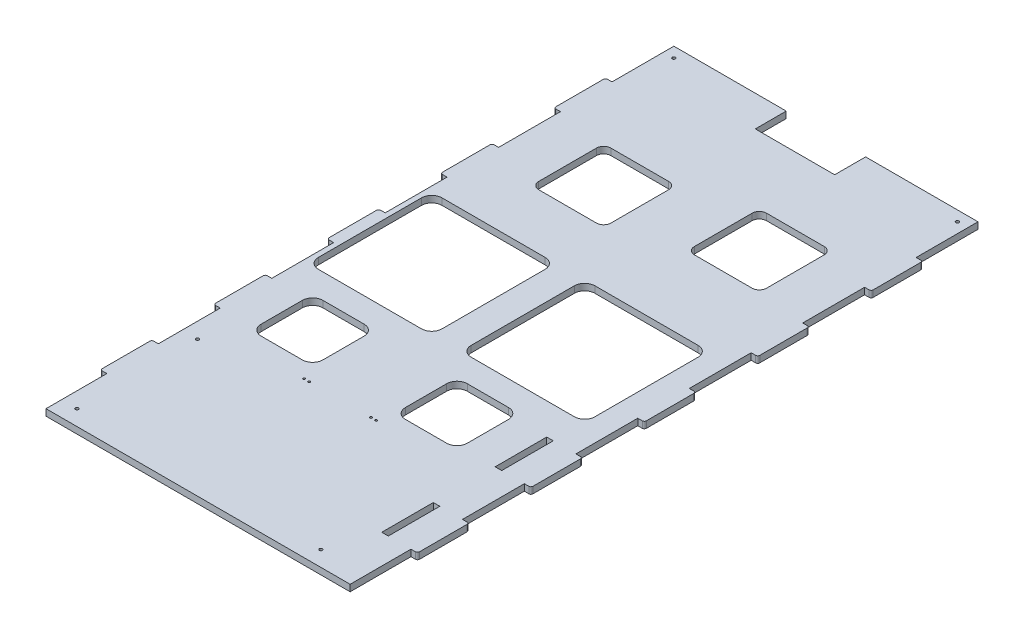
SolidWorks part; units mm, degrees
material "Beech"
ref_plane "Front Plane" through (0, 0, 0) normal (0, 0, 1) x (1, 0, 0)
ref_plane "Top Plane" through (0, 0, 0) normal (0, 1, 0) x (1, 0, 0)
ref_plane "Right Plane" through (0, 0, 0) normal (1, 0, 0) x (0, 0, -1)
sketch "Sketch1" plane through (0, 0, 0) normal (0, 1, 0) x (1, 0, 0)
  line L1 (0, 0) -> (295, 0)
  line L2 (0, 0) -> (0, 59)
  line L3 (0, 609) -> (295, 609)
  line L4 (295, 0) -> (295, 59)
  line L5 (0, 59) -> (-6.35, 59)
  line L7 (0, 109) -> (-6.35, 109)
  line L8 (-6.35, 59) -> (-6.35, 109)
  line L9 (0, 169) -> (-6.35, 169)
  line L10 (-6.35, 169) -> (-6.35, 219)
  line L11 (0, 219) -> (-6.35, 219)
  line L13 (0, 279) -> (-6.35, 279)
  line L14 (-6.35, 279) -> (-6.35, 329)
  line L15 (0, 329) -> (-6.35, 329)
  line L17 (0, 389) -> (-6.35, 389)
  line L18 (-6.35, 389) -> (-6.35, 439)
  line L19 (0, 439) -> (-6.35, 439)
  line L21 (0, 499) -> (-6.35, 499)
  line L22 (-6.35, 499) -> (-6.35, 549)
  line L23 (0, 549) -> (-6.35, 549)
  line L25 (295, 59) -> (301.35, 59)
  line L27 (295, 109) -> (301.35, 109)
  line L28 (301.35, 59) -> (301.35, 109)
  line L29 (295, 169) -> (301.35, 169)
  line L30 (301.35, 169) -> (301.35, 219)
  line L31 (295, 219) -> (301.35, 219)
  line L33 (295, 279) -> (301.35, 279)
  line L34 (301.35, 279) -> (301.35, 329)
  line L35 (295, 329) -> (301.35, 329)
  line L37 (295, 389) -> (301.35, 389)
  line L38 (301.35, 389) -> (301.35, 439)
  line L39 (295, 439) -> (301.35, 439)
  line L41 (295, 499) -> (301.35, 499)
  line L42 (301.35, 499) -> (301.35, 549)
  line L43 (295, 549) -> (301.35, 549)
  line L44 (0, 549) -> (0, 609)
  line L46 (0, 329) -> (0, 389)
  line L49 (0, 219) -> (0, 279)
  line L50 (0, 109) -> (0, 169)
  line L51 (295, 109) -> (295, 169)
  line L52 (295, 219) -> (295, 279)
  line L53 (295, 329) -> (295, 389)
  line L54 (295, 439) -> (295, 499)
  line L55 (295, 549) -> (295, 609)
  line L56 (0, 439) -> (0, 499)
  dimension "D1" = 609
  dimension "D2" = 295
  dimension "D3" = 6.35
  dimension "D4" = 50
  dimension "D5" = 59
  dimension "D7" = 60
  dimension "D8" = 50
  dimension "D9" = 6.35
  dimension "D11" = 59
  dimension "D12" = 60
  dimension "D6" = 5
  dimension "D10" = 5
extrude "Boss-Extrude1" add sketch "Sketch1" along normal blind 6.35
fillet "Fillet1" radius 2 20 edges at (301.35, 3.175, -549) (301.35, 3.175, -499) (301.35, 3.175, -439) (301.35, 3.175, -389) (301.35, 3.175, -329) (301.35, 3.175, -279) (301.35, 3.175, -219) (301.35, 3.175, -169) (301.35, 3.175, -109) (301.35, 3.175, -59) (-6.35, 3.175, -59) (-6.35, 3.175, -109) (-6.35, 3.175, -169) (-6.35, 3.175, -219) (-6.35, 3.175, -279) (-6.35, 3.175, -329) (-6.35, 3.175, -389) (-6.35, 3.175, -439) (-6.35, 3.175, -499) (-6.35, 3.175, -549)
sketch "Sketch2" plane through (0, 6.35, 0) normal (0, 1, 0) x (1, 0, 0)
  line L0 (266.65, 0) -> (266.65, 100) construction
  line L1 (0, 0) -> (295, 0) construction
  line L2 (0, 609) -> (0, 0) construction
  line L3 (295, 609) -> (295, 0) construction
  line L4 (0, 150) -> (266.65, 100) construction
  line L5 (266.65, 169) -> (266.65, 219)
  line L6 (266.65, 59) -> (273, 59)
  line L7 (266.65, 59) -> (266.65, 109)
  line L8 (266.65, 109) -> (273, 109)
  line L9 (273, 59) -> (273, 109)
  line L10 (266.65, 169) -> (273, 169)
  line L11 (273, 169) -> (273, 219)
  line L12 (266.65, 219) -> (273, 219)
  line L13 (0, 84.2124) -> (266.65, 84) construction
  line L14 (55.0424, 492.8768) -> (111.0424, 492.8768)
  line L15 (48.0424, 485.8768) -> (48.0424, 429.8768)
  line L16 (55.0424, 422.8768) -> (111.0424, 422.8768)
  line L17 (118.0424, 485.8768) -> (118.0424, 429.8768)
  line L18 (185.2335, 513.6581) -> (241.2335, 513.6581)
  line L19 (178.2335, 506.6581) -> (178.2335, 450.6581)
  line L20 (185.2335, 443.6581) -> (241.2335, 443.6581)
  line L21 (248.2335, 506.6581) -> (248.2335, 450.6581)
  line L22 (43.325, 225.298) -> (83.325, 225.298)
  line L23 (33.325, 215.298) -> (33.325, 175.298)
  line L24 (43.325, 165.298) -> (83.325, 165.298)
  line L25 (93.325, 215.298) -> (93.325, 175.298)
  line L26 (33.325, 225.298) -> (93.325, 165.298) construction
  line L27 (33.325, 165.298) -> (93.325, 225.298) construction
  line L32 (133.325, 0) -> (133.325, 609) construction
  line L33 (295, 609) -> (0, 609) construction
  line L34 (5, 369.1536) -> (125, 369.1536)
  line L35 (5, 369.1536) -> (5, 249.1536)
  line L36 (5, 249.1536) -> (125, 249.1536)
  line L37 (125, 369.1536) -> (125, 249.1536)
  line L38 (153, 369.4528) -> (273, 369.4528)
  line L39 (153, 369.4528) -> (153, 249.4528)
  line L40 (153, 249.4528) -> (273, 249.4528)
  line L41 (273, 369.4528) -> (273, 249.4528)
  line L42 (233.325, 165.298) -> (173.325, 225.298) construction
  line L43 (233.325, 225.298) -> (173.325, 165.298) construction
  line L44 (173.325, 215.298) -> (173.325, 175.298)
  line L45 (223.325, 165.298) -> (183.325, 165.298)
  line L46 (233.325, 215.298) -> (233.325, 175.298)
  line L47 (223.325, 225.298) -> (183.325, 225.298)
  line L48 (100, 150.298) -> (105, 150.298) construction
  line L49 (105, 150.298) -> (165, 150.298) construction
  line L50 (165, 150.298) -> (170, 150.298) construction
  line L51 (147.5, 609) -> (147.5, 0) construction
  line L52 (109, 609) -> (186, 609)
  line L53 (109, 609) -> (109, 579)
  line L54 (109, 579) -> (186, 579)
  line L55 (186, 609) -> (186, 579)
  line L56 (147.5, 609) -> (147.5, 579) construction
  arc A0 (48.0424, 429.8768) -> (55.0424, 422.8768) centre (55.0424, 429.8768) ccw
  arc A1 (111.0424, 422.8768) -> (118.0424, 429.8768) centre (111.0424, 429.8768) ccw
  arc A2 (111.0424, 492.8768) -> (118.0424, 485.8768) centre (111.0424, 485.8768) cw
  arc A3 (55.0424, 492.8768) -> (48.0424, 485.8768) centre (55.0424, 485.8768) ccw
  arc A4 (178.2335, 450.6581) -> (185.2335, 443.6581) centre (185.2335, 450.6581) ccw
  arc A5 (241.2335, 443.6581) -> (248.2335, 450.6581) centre (241.2335, 450.6581) ccw
  arc A6 (241.2335, 513.6581) -> (248.2335, 506.6581) centre (241.2335, 506.6581) cw
  arc A7 (185.2335, 513.6581) -> (178.2335, 506.6581) centre (185.2335, 506.6581) ccw
  arc A8 (33.325, 175.298) -> (43.325, 165.298) centre (43.325, 175.298) ccw
  arc A9 (83.325, 165.298) -> (93.325, 175.298) centre (83.325, 175.298) ccw
  arc A10 (83.325, 225.298) -> (93.325, 215.298) centre (83.325, 215.298) cw
  arc A11 (43.325, 225.298) -> (33.325, 215.298) centre (43.325, 215.298) ccw
  arc A16 (223.325, 225.298) -> (233.325, 215.298) centre (223.325, 215.298) cw
  arc A17 (183.325, 225.298) -> (173.325, 215.298) centre (183.325, 215.298) ccw
  arc A18 (183.325, 165.298) -> (173.325, 175.298) centre (183.325, 175.298) cw
  arc A19 (233.325, 175.298) -> (223.325, 165.298) centre (223.325, 175.298) cw
  circle A20 centre (15, 15) radius 1.5
  circle A21 centre (251.65, 15) radius 1.5
  circle A22 centre (15, 131.9259) radius 1.5
  circle A23 centre (10, 599) radius 1.5
  circle A24 centre (285, 599) radius 1.5
  circle A25 centre (100, 150.298) radius 1.025
  circle A26 centre (105, 150.298) radius 1.025
  circle A27 centre (165, 150.298) radius 1.025
  circle A28 centre (170, 150.298) radius 1.025
  point P33 (118.0424, 422.8768)
  point P36 (118.0424, 492.8768)
  point P39 (48.0424, 492.8768)
  point P42 (178.2335, 443.6581)
  point P47 (248.2335, 513.6581)
  point P50 (178.2335, 513.6581)
  point P51 (63.325, 195.298)
  point P74 (133.325, 84.1062)
  point P99 (203.325, 195.298)
  point P129 (33.325, 542.4309)
  point P131 (61.5957, 551.3213)
  point P132 (106.5302, 609)
  point P133 (103.8692, 609)
  dimension "D10" = 7
  dimension "D11" = 7
  dimension "D16" = 10
  dimension "D17" = 70
  dimension "D22" = 3
  dimension "D25" = 3
  dimension "D28" = 3
  dimension "D18" = 3
  dimension "D31" = 3
  dimension "D40" = 2.05
  dimension "D42" = 2.05
  dimension "D43" = 2.05
  dimension "D44" = 2.05
  dimension "D1" = 100
  dimension "D2" = 150
  dimension "D3" = 6.35
  dimension "D4" = 50
  dimension "D6" = 70
  dimension "D7" = 70
  dimension "D8" = 70
  dimension "D9" = 70
  dimension "D12" = 60
  dimension "D13" = 60
  dimension "D14" = 22
  dimension "D15" = 59
  dimension "12" = 120
  dimension "D19" = 120
  dimension "D20" = 120
  dimension "D21" = 120
  dimension "D23" = 15
  dimension "D24" = 15
  dimension "D26" = 15
  dimension "D27" = 15
  dimension "D29" = 15
  dimension "D30" = 15
  dimension "D32" = 10
  dimension "D33" = 10
  dimension "D34" = 10
  dimension "D35" = 10
  dimension "D36" = 5
  dimension "D37" = 22
  dimension "D38" = 15
  dimension "D39" = 200
  dimension "D41" = 5
  dimension "D45" = 5
  dimension "D46" = 60
  dimension "D47" = 30
  dimension "D48" = 77
  dimension "D5" = 2
extrude "Cut-Extrude1" cut sketch "Sketch2" against normal blind 6.35
fillet "Fillet2" radius 10 8 edges at (125, 3.175, -249.1536) (5, 3.175, -249.1536) (5, 3.175, -369.1536) (125, 3.175, -369.1536) (153, 3.175, -249.4528) (273, 3.175, -249.4528) (273, 3.175, -369.4528) (153, 3.175, -369.4528)
